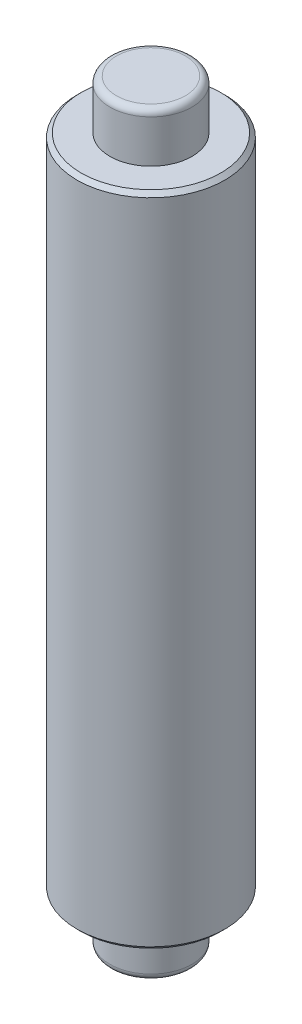
SolidWorks part; units mm, degrees
ref_plane "Front Plane" through (0, 0, 0) normal (0, 0, 1) x (1, 0, 0)
ref_plane "Top Plane" through (0, 0, 0) normal (0, 1, 0) x (1, 0, 0)
ref_plane "Right Plane" through (0, 0, 0) normal (1, 0, 0) x (0, 0, -1)
sketch "Sketch1" plane through (0, 0, 0) normal (0, 1, 0) x (1, 0, 0)
  circle A0 centre (0, 0) radius 2.5
  dimension "D1" = 5
extrude "Boss-Extrude1" add sketch "Sketch1" along normal blind 46
fillet "Fillet5" radius 0.4 2 edges at (0, 0, 2.5) (0, 46, 2.5)
ref_plane "Plane1" through (0, 23, 0) normal (0, 1, 0) x (1, 0, 0)
sketch "Sketch2" plane through (0, 23, 0) normal (0, 1, 0) x (1, 0, 0)
  circle A0 centre (0, 0) radius 4.5
  dimension "D1" = 9
extrude "Boss-Extrude2" add sketch "Sketch2" along normal mid plane 40
chamfer "Chamfer1" distance 0.25 angle 45 2 edges at (0, 3, 4.5) (0, 43, 4.5)
